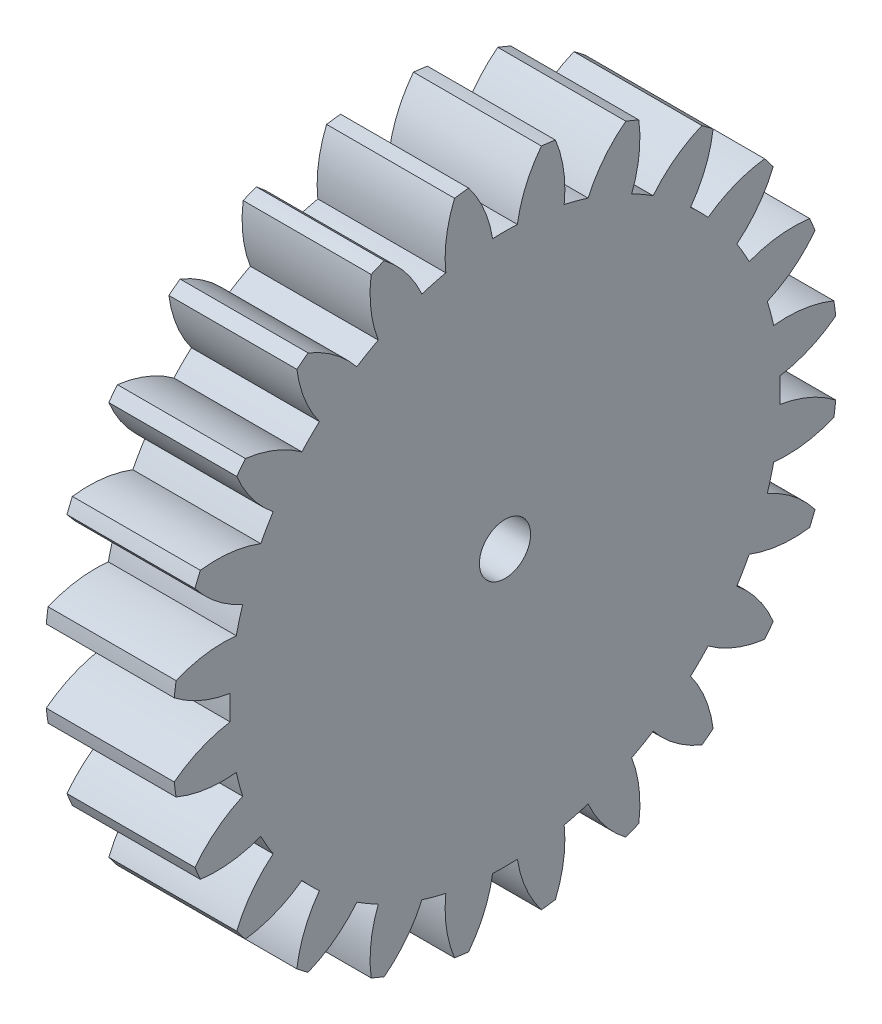
SolidWorks part; units mm, degrees
material "1.0035 (S185)"
ref_plane "Plane1" through (0, 0, 0) normal (0, 0, 1) x (1, 0, 0)
ref_plane "Plane2" through (0, 0, 0) normal (0, 1, 0) x (1, 0, 0)
ref_plane "Plane3" through (0, 0, 0) normal (1, 0, 0) x (0, 0, -1)
sketch "HoldingSke" plane through (0, 0, 0) normal (0, 1, 0) x (1, 0, 0)
  line L0 (0, 0) -> (0.9135, -0.4067)
  line L1 (-15, 0) -> (100, 0) construction
  line L2 (0, 0) -> (-2.1039, 2.3779)
  line L3 (0, 0) -> (-11.863, 4.5341)
  line L4 (0, 0) -> (7.8894, 3.5126)
  line L5 (0, 0) -> (-46.8476, -17.4728)
  line L6 (0, 0) -> (-4.1448, -2.7965)
  line L7 (-2.1039, 2.3779) -> (8.6586, 51.2059)
  line L8 (-76.2, 54.61) -> (-75.9, 54.61)
  line L9 (-71.009, 38.7566) -> (-53.1078, 45.2721)
  line L10 (-76.2, 71.12) -> (104.1128, 71.12)
  line L11 (0, 0) -> (-5, 0)
  line L12 (-76.2, 101.6) -> (-76.162, 101.6)
  line L13 (24.9733, 27.94) -> (52.9518, 28.4284)
  line L14 (24.9733, 27.94) -> (24.9743, 27.94)
  line L15 (24.9733, 27.94) -> (100.4006, 29.5858)
  line L16 (-63.627, -1) -> (-12.827, -1)
  circle A0 centre (0, 0) radius 1
  circle A1 centre (0, 0) radius 10.749
  circle A2 centre (0, 0) radius 37.5
  circle A3 centre (0, 0) radius 1
  dimension "MHD" = 21.498
  dimension "Hub_dia" = 75
  dimension "Bore" = 2
  dimension "MBD" = 2
  dimension "Num_teeth" = 24
  dimension "Pitch_radius" = 180.3128
  dimension "Pitch" = 1
  dimension "Width" = 5
  dimension "Overall_len" = 50
  dimension "Show_teeth" = 24
  dimension "Thickness" = 5
  dimension "OAL" = 50.0001
  dimension "T_dim" = 0.3
  dimension "Ap" = 20
  dimension "H" = 19.05
  dimension "Backlash" = 0.038
  dimension "Addendum_fac" = 1
  dimension "Dedendum_fac" = 1.25
  dimension "Clearance_fac" = 0.25
  dimension "Dedendum_add" = 0.001
  dimension "Module" = 1
sketch "BasProSke" plane through (0, 0, 0) normal (0, 1, 0) x (1, 0, 0)
  line L0 (-10, 0) -> (60, 0) construction
  line L1 (0, 0) -> (0, 13)
  line L2 (0, 0) -> (5, 0)
  line L3 (5, 0) -> (5, 13)
  line L4 (5, 13) -> (0, 13)
  dimension "Diameter" = 26
  dimension "Thickness" = 5
revolve "Base-Revolve" add sketch "BasProSke" angle 360 about L0
sketch "TooCutSke" plane through (0, 0, 0) normal (1, 0, 0) x (0, 0, -1)
  line L1 (0, 0) -> (0, 107) construction
  line L2 (0, 0) -> (-0.8513, 11.9698) construction
  line L3 (0, 0) -> (-3.127, 23.752) construction
  line L4 (-0.8513, 11.9698) -> (-1.5635, 11.876) construction
  arc A0 (0.4834, 10.7381) -> (-0.4834, 10.7381) centre (0, 0) ccw
  arc A1 (1.4409, 12.9455) -> (-1.4409, 12.9455) centre (0, 0) ccw
  circle A2 centre (0, 0) radius 12 construction
  circle A3 centre (0, 0) radius 11.2763 construction
  arc A4 (-0.4834, 10.7381) -> (-1.4409, 12.9455) centre (-5.2252, 9.9926) ccw
  arc A5 (1.4409, 12.9455) -> (0.4834, 10.7381) centre (5.2252, 9.9926) ccw
  dimension "Root_dia" = 21.498
  dimension "Overcut_dia" = 26.0508
  dimension "Pitch_dia" = 24
  dimension "Base_dia" = 22.5526
  dimension "Flank_rad" = 4.8
  dimension "Half_ang" = 7.5
  dimension "Half_CT" = 0.7183
extrude "ToothCut" cut sketch "TooCutSke" along normal through all
fillet "Breaks" [suppressed] radius 0.02 tangent propagation no
fillet "RootFillets" [suppressed] radius 0.251
pattern_circular "TeethCuts" count 24 every 15 about axis through (-10, 0, 0) along (1, 0, 0) of "ToothCut", "RootFillets", "Breaks"
sketch "HubNeaOneSke" plane through (0, 0, 0) normal (-1, 0, 0) x (0, 0, 1)
  circle A0 centre (0, 0) radius 10.749
  dimension "Diameter" = 21.498
extrude "HubNearOne" [suppressed] add sketch "HubNeaOneSke" along normal blind 45.0001
sketch "HubNeaBotSke" plane through (0, 0, 0) normal (-1, 0, 0) x (0, 0, 1)
  circle A0 centre (0, 0) radius 10.749
  dimension "Diameter" = 21.498
extrude "HubNearBoth" [suppressed] add sketch "HubNeaBotSke" along normal blind 22.5
ref_plane "FarPln" through (5, 0, 0) normal (1, 0, 0) x (0, 0, -1)
sketch "HubFarSke" plane through (5, 0, 0) normal (1, 0, 0) x (0, 0, -1)
  circle A0 centre (0, 0) radius 10.749
  dimension "Diameter" = 21.498
extrude "HubFar" [suppressed] add sketch "HubFarSke" along normal blind 22.5
sketch "BorSke" plane through (0, 0, 0) normal (1, 0, 0) x (0, 0, -1)
  circle A0 centre (0, 0) radius 1
  dimension "Diameter" = 2
extrude "Bore" cut sketch "BorSke" along normal mid plane 100.0001
sketch "KeySke" plane through (0, 0, 0) normal (1, 0, 0) x (0, 0, -1)
  line L0 (-0.4, 0) -> (-0.4, 1.3)
  line L1 (-0.4, 1.3) -> (0.4, 1.3)
  line L2 (0.4, 1.3) -> (0.4, 0)
  line L3 (0, 0) -> (0, 34) construction
  line L4 (-0.4, 0) -> (0.4, 0)
  dimension "Offset" = 1.3
  dimension "Width" = 0.8
extrude "Keyway" [suppressed] cut sketch "KeySke" along normal mid plane 100.0001
pattern_circular "Keyway2" [suppressed] count 2 every 90 about axis through (-10, 0, 0) along (1, 0, 0)
ref_axis "Achse1" through (5, 0, 0) along (-1, 0, 0)
equation "' \"Module@HoldingSke\" = 6.35"
equation "' \"Num_teeth@HoldingSke\" = 12"
equation "' \"Ap@HoldingSke\" =  20"
equation "' \"Width@HoldingSke\" = 0.5 * 25.4"
equation "' \"Hub_dia@HoldingSke\"= 1 * 25.4"
equation "' \"Overall_len@HoldingSke\" = 1.0 * 25.4"
equation "' \"Bore@HoldingSke\" = 0.75 * 25.4"
equation "' \"T_dim@HoldingSke\" = 0.1 * 25.4"
equation "' \"Width@KeySke\" = 0.25 * 25.4"
equation "' \"Show_teeth@HoldingSke\" = 13"
equation "' \"Backlash@HoldingSke\" = 0.009 * 25.4"
equation "' \"Addendum_fac@HoldingSke\" = 1.0"
equation "' \"Dedendum_fac@HoldingSke\" = 1.25"
equation "' \"Dedendum_add@HoldingSke\" = 0.00005 * 25.4"
equation "' \"Clearance_fac@HoldingSke\" = 0.25"
equation "\"Pitch@HoldingSke\" = 1 / \"Module@HoldingSke\""
equation "\"Overcut_dia@TooCutSke\" = (\"Num_teeth@HoldingSke\" + 2 * \"Addendum_fac@HoldingSke\") / \"Pitch@HoldingSke\" + 0.002 * 25.4"
equation "\"Pitch_dia@TooCutSke\" = \"Num_teeth@HoldingSke\" / \"Pitch@HoldingSke\""
equation "\"Base_dia@TooCutSke\" = \"Num_teeth@HoldingSke\" / \"Pitch@HoldingSke\" * cos((\"Ap@HoldingSke\"  * 3.14159265 / 180))"
equation "\"Root_dia@TooCutSke\" = (\"Num_teeth@HoldingSke\" + 2) / \"Pitch@HoldingSke\" - 2 * (\"Addendum_fac@HoldingSke\" + \"Dedendum_fac@HoldingSke\") / \"Pitch@HoldingSke\" - \"Dedendum_add@HoldingSke\" * 2"
equation "\"Half_ang@TooCutSke\" = 180 / \"Num_teeth@HoldingSke\""
equation "\"Half_CT@TooCutSke\" = \"Num_teeth@HoldingSke\" / \"Pitch@HoldingSke\" * sin((3.14159265 / 2 / \"Num_teeth@HoldingSke\")) / 2 - 7 * \"Backlash@HoldingSke\" / 4"
equation "\"Flank_rad@TooCutSke\" = \"Num_teeth@HoldingSke\" / \"Pitch@HoldingSke\" / 5"
equation "\"Radius@RootFillets\" = \"Clearance_fac@HoldingSke\" / \"Pitch@HoldingSke\" + \"Dedendum_add@HoldingSke\""
equation "\"Break_rad@Breaks\" = 0.02 / \"Pitch@HoldingSke\""
equation "\"Thickness@HoldingSke\" = \"Width@HoldingSke\""
equation "\"OAL@HoldingSke\" = \"Thickness@HoldingSke\""
equation "\"MHD@HoldingSke\" = (\"Num_teeth@HoldingSke\" + 2) / \"Pitch@HoldingSke\" - 2 * (\"Addendum_fac@HoldingSke\" + \"Dedendum_fac@HoldingSke\")  / \"Pitch@HoldingSke\" - \"Dedendum_add@HoldingSke\" * 2"
equation "\"MBD@HoldingSke\" = (\"Num_teeth@HoldingSke\" + 2) / \"Pitch@HoldingSke\" - 2 * (\"Addendum_fac@HoldingSke\" + \"Dedendum_fac@HoldingSke\")  / \"Pitch@HoldingSke\" - \"Dedendum_add@HoldingSke\" * 2 - 0.002 * 25.4"
equation "\"MHD@HoldingSke\" = ((sgn( \"MHD@HoldingSke\" - \"Hub_dia@HoldingSke\" )-1)*( \"MHD@HoldingSke\" - \"Hub_dia@HoldingSke\" ))/-2+ \"Hub_dia@HoldingSke\""
equation "\"MBD@HoldingSke\" = ((sgn( \"MBD@HoldingSke\" - \"Bore@HoldingSke\" )-1)*( \"MBD@HoldingSke\" - \"Bore@HoldingSke\" ))/-2+ \"Bore@HoldingSke\""
equation "\"OAL@HoldingSke\" = ((sgn( \"OAL@HoldingSke\" - \"Overall_len@HoldingSke\" )+1)*( \"OAL@HoldingSke\" - \"Overall_len@HoldingSke\" ))/2 + \"Overall_len@HoldingSke\" + 0.000002 * 25.4"
equation "\"Num_teeth@TeethCuts\" = int( \"Show_teeth@HoldingSke\" ) + 1"
equation "\"Num_teeth@TeethCuts\" = ((sgn( \"Num_teeth@TeethCuts\" - \"Num_teeth@HoldingSke\" )-1)*( \"Num_teeth@TeethCuts\" - \"Num_teeth@HoldingSke\" ))/-2+ \"Num_teeth@HoldingSke\""
equation "\"Num_teeth@TeethCuts\" = ((sgn( \"Num_teeth@TeethCuts\" - 2.0)+1)*( \"Num_teeth@TeethCuts\" - 2.0))/2 +2.0"
equation "\"Angle@TeethCuts\" = 360.0 / \"Num_teeth@HoldingSke\""
equation "\"Diameter@BasProSke\" = (\"Num_teeth@HoldingSke\" + 2 * \"Addendum_fac@HoldingSke\") / \"Pitch@HoldingSke\""
equation "\"Thickness@BasProSke\"  = \"Thickness@HoldingSke\""
equation "' \"Fillet_rad@BasProSke\" =  \"Thickness@HoldingSke\" * 0.05"
equation "\"MHD@HoldingSke\" = ((sgn( \"MHD@HoldingSke\" - \"Root_dia@TooCutSke\" )-1)*( \"MHD@HoldingSke\" - \"Root_dia@TooCutSke\" ))/-2+ \"Root_dia@TooCutSke\""
equation "\"Diameter@HubNeaOneSke\" = \"MHD@HoldingSke\""
equation "\"Length@HubNearOne\" = \"OAL@HoldingSke\" - \"Thickness@BasProSke\""
equation "\"Diameter@HubNeaBotSke\" = \"MHD@HoldingSke\""
equation "\"Length@HubNearBoth\" = ( \"OAL@HoldingSke\" - \"Thickness@BasProSke\" ) / 2.0"
equation "\"Thickness@FarPln\" = \"Thickness@BasProSke\""
equation "\"Diameter@HubFarSke\" = \"MHD@HoldingSke\""
equation "\"Length@HubFar\" = ( \"OAL@HoldingSke\" - \"Thickness@BasProSke\" ) / 2.0"
equation "\"Diameter@BorSke\" = \"MBD@HoldingSke\""
equation "\"D1@Bore\" = \"OAL@HoldingSke\" * 2.0"
equation "\"D1@Keyway\" = \"OAL@HoldingSke\" * 2.0"
equation "\"Offset@KeySke\" = \"T_dim@HoldingSke\" + \"MBD@HoldingSke\" / 2.0"
